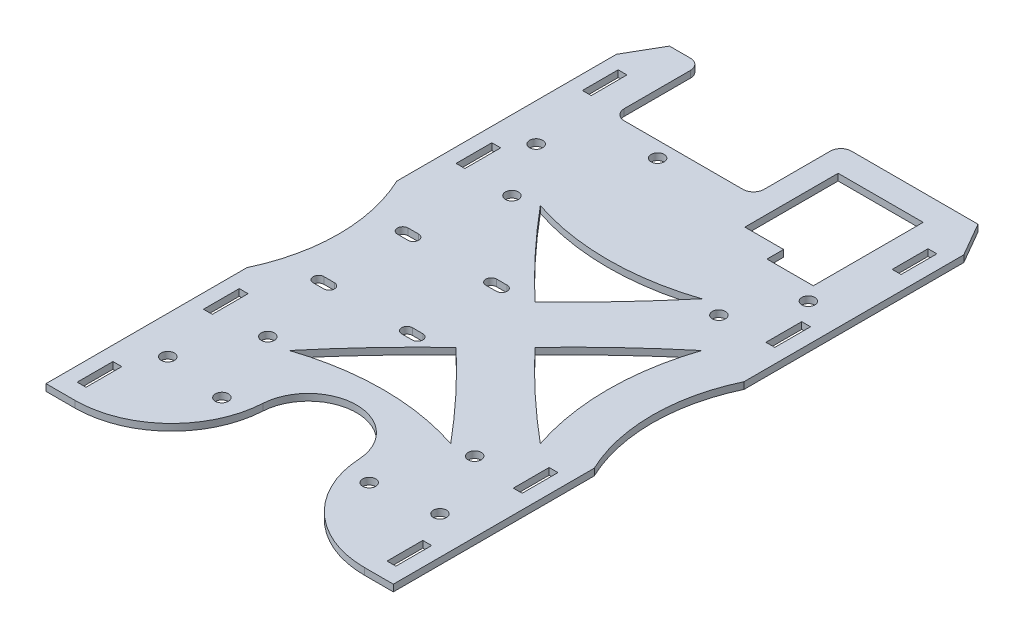
SolidWorks part; units mm, degrees
ref_plane "Front Plane" through (0, 0, 0) normal (0, 0, 1) x (1, 0, 0)
ref_plane "Top Plane" through (0, 0, 0) normal (0, 1, 0) x (1, 0, 0)
ref_plane "Right Plane" through (0, 0, 0) normal (1, 0, 0) x (0, 0, -1)
sketch "Sketch1" plane through (0, 0, 0) normal (0, 1, 0) x (1, 0, 0)
  line L0 (-1000, 0) -> (49000, 0) construction
  line L1 (0, 0) -> (0, 100.3728) construction
  line L5 (-41.25, -55) -> (-34.3696, -55)
  line L6 (41.25, -55) -> (34.3696, -55)
  line L7 (9.55, 82.35) -> (29.75, 82.35)
  line L8 (29.75, 82.35) -> (29.75, 56.25)
  line L10 (9.55, 60.2) -> (9.55, 82.35)
  line L11 (35.75, 77.5) -> (37.85, 77.5)
  line L12 (37.85, 77.5) -> (37.85, 69)
  line L13 (37.85, 69) -> (35.75, 69)
  line L14 (35.75, 69) -> (35.75, 77.5)
  line L15 (35.75, 39) -> (35.75, 47.5)
  line L16 (35.75, 47.5) -> (37.85, 47.5)
  line L17 (37.85, 47.5) -> (37.85, 39)
  line L18 (37.85, 39) -> (35.75, 39)
  line L19 (35.75, 9) -> (35.75, 17.5) construction
  line L20 (35.75, 17.5) -> (37.85, 17.5) construction
  line L21 (37.85, 17.5) -> (37.85, 9) construction
  line L22 (37.85, 9) -> (35.75, 9) construction
  line L35 (35.75, -51) -> (35.75, -42.5)
  line L36 (35.75, -42.5) -> (37.85, -42.5)
  line L37 (37.85, -42.5) -> (37.85, -51)
  line L38 (-41.25, -55) -> (-41.25, 0)
  line L39 (9.55, 60.2) -> (18.75, 60.2)
  line L40 (37.85, -51) -> (35.75, -51)
  line L42 (18.75, 56.25) -> (18.75, 60.2)
  line L43 (-37.85, -51) -> (-37.85, -42.5)
  line L44 (-37.85, -42.5) -> (-35.75, -42.5)
  line L45 (-41.25, 0) -> (-41.25, 80.5)
  line L46 (41.25, -55) -> (41.25, 0)
  line L47 (41.25, 0) -> (41.25, 80.5)
  line L48 (-41.25, 80.5) -> (-36.6408, 88.4834)
  line L49 (-36.6408, 88.4834) -> (36.6408, 88.4834)
  line L50 (41.25, 80.5) -> (36.6408, 88.4834)
  line L51 (35.75, -21) -> (35.75, -12.5)
  line L52 (35.75, -12.5) -> (37.85, -12.5)
  line L53 (37.85, -12.5) -> (37.85, -21)
  line L54 (37.85, -21) -> (35.75, -21)
  line L55 (35.75, 69) -> (35.75, 39) construction
  line L56 (-37.85, 69) -> (-37.85, 77.5)
  line L57 (-37.85, 77.5) -> (-35.75, 77.5)
  line L58 (-35.75, 77.5) -> (-35.75, 69)
  line L59 (-35.75, 69) -> (-37.85, 69)
  line L60 (-37.85, 39) -> (-37.85, 47.5)
  line L61 (-37.85, 47.5) -> (-35.75, 47.5)
  line L62 (-35.75, 47.5) -> (-35.75, 39)
  line L63 (-35.75, 39) -> (-37.85, 39)
  line L64 (-37.85, 9) -> (-37.85, 17.5) construction
  line L65 (-37.85, 17.5) -> (-35.75, 17.5) construction
  line L66 (-35.75, 17.5) -> (-35.75, 9) construction
  line L67 (-35.75, 9) -> (-37.85, 9) construction
  line L68 (-37.85, -21) -> (-37.85, -12.5)
  line L69 (-37.85, -12.5) -> (-35.75, -12.5)
  line L70 (-35.75, -12.5) -> (-35.75, -21)
  line L71 (-35.75, -21) -> (-37.85, -21)
  line L72 (18.75, 56.25) -> (29.75, 56.25)
  line L74 (-35.75, -42.5) -> (-35.75, -51)
  line L75 (-35.75, -51) -> (-37.85, -51)
  circle A2 centre (-15, 64.0223) radius 1.55
  circle A3 centre (-17.5, -36.9777) radius 1.55
  circle A6 centre (17.5, -36.9777) radius 1.55
  arc A7 (-11.4407, -33.3184) -> (-34.3696, -55) centre (-34.3696, -32.0353) cw
  arc A8 (-11.4407, -33.3184) -> (0, -22.5) centre (0, -33.9586) cw
  arc A9 (11.4407, -33.3184) -> (34.3696, -55) centre (34.3696, -32.0353) ccw
  arc A10 (11.4407, -33.3184) -> (0, -22.5) centre (0, -33.9586) ccw
  circle A11 centre (32.325, 52.5) radius 2.75 construction
  circle A12 centre (32.325, 52.5) radius 1.55
  circle A13 centre (32.325, -35) radius 1.55
  circle A14 centre (32.325, -35) radius 2.75 construction
  circle A15 centre (-32.325, 52.5) radius 1.55
  circle A16 centre (-32.325, -35) radius 1.55
  circle A17 centre (-32.325, 52.5) radius 2.75 construction
  circle A18 centre (-32.325, -35) radius 2.75 construction
  circle A19 centre (-24.575, 39) radius 1.55
  circle A20 centre (24.575, 39) radius 1.55
  circle A21 centre (24.575, -19) radius 1.55
  circle A22 centre (-24.575, -19) radius 1.55
  point P20 (-41.25, 0)
  point P23 (0, 55)
  point P26 (41.25, 0)
  point P63 (24.25, 56.25)
  point P83 (0, 88.4834)
  dimension "D20" = 5.5
  dimension "D21" = 3.1
  dimension "D22" = 64.65
  dimension "D4" = 101
  dimension "D5" = 17.5
  dimension "D6" = 15
  dimension "D7" = 64.0223
  dimension "D8" = 120
  dimension "D9" = 55
  dimension "D10" = 2
  dimension "D11" = 5
  dimension "D12" = 2.1
  dimension "D13" = 80.5
  dimension "D14" = 82.5
  dimension "D15" = 8.5
  dimension "D16" = 77.5
  dimension "D17" = 30
  dimension "D18" = 71.5
  dimension "D19" = 22.5
  dimension "D23" = 3.425
  dimension "D24" = 52.5
  dimension "D25" = 35
  dimension "D26" = 9.55
  dimension "D27" = 29.75
  dimension "D28" = 82.35
  dimension "D29" = 3.95
  dimension "D30" = 9.2
  dimension "D31" = 26.1
  dimension "D32" = 49.15
  dimension "D33" = 58
  dimension "D34" = 39
extrude "主结构和连接" add sketch "Sketch1" along normal blind 1.6 contours A10 A9 L6 L46 L47 L50 L49 L48 L45 L38 L5 A7 A8 L72 L42 L39 L10 L7 L8 L20 L21 L17 L12 L13 L14 L15 L19 region at (-0.9568, 0, -19.3532)
sketch "外部切除点示意-1" plane through (0, 0, 0) normal (0, 1, 0) x (1, 0, 0)
  line L0 (-36.6408, 88.4834) -> (36.6408, 88.4834) construction
  line L1 (0, 0) -> (-149.6598, 0) construction
  line L2 (0, -1000) -> (0, 49000) construction
  line L3 (-41.25, 28.3195) -> (-41.2859, -7.3505)
  line L4 (41.25, 28.3195) -> (41.2859, -7.3505)
  line L5 (4.0667, 88.4834) -> (4.0667, 67.7334)
  line L7 (4.0667, 67.7334) -> (-29.1468, 67.7334)
  line L8 (-29.1468, 67.7334) -> (-29.1468, 88.4834)
  line L10 (-29.1468, 88.4834) -> (4.0667, 88.4834)
  arc A0 (-41.25, 28.3195) -> (-41.2859, -7.3505) centre (-78.8424, 10.5223) cw
  arc A3 (41.25, 28.3195) -> (41.2859, -7.3505) centre (78.8424, 10.5223) ccw
  dimension "D1" = 20.75
extrude "底板让位" cut sketch "外部切除点示意-1" along normal through all
sketch "电源模块接口-草图" plane through (0, 0, 0) normal (0, 1, 0) x (1, 0, 0)
  line L0 (-32.25, 18.75) -> (-4.75, 18.75) construction
  line L1 (-4.75, 18.75) -> (-4.75, -1.25) construction
  line L2 (-4.75, -1.25) -> (-32.25, -1.25) construction
  line L3 (-32.25, -1.25) -> (-32.25, 18.75) construction
  line L4 (-30.25, 18.75) -> (-27.75, 18.75) construction
  line L5 (-30.25, 20.025) -> (-27.75, 20.025)
  line L6 (-30.25, 17.475) -> (-27.75, 17.475)
  line L7 (-18.5, 18.75) -> (-18.5, -1.25) construction
  line L8 (-32.25, 8.75) -> (-4.75, 8.75) construction
  line L9 (-6.75, 18.75) -> (-9.25, 18.75) construction
  line L10 (-6.75, 20.025) -> (-9.25, 20.025)
  line L11 (-6.75, 17.475) -> (-9.25, 17.475)
  line L12 (-30.25, -1.25) -> (-27.75, -1.25) construction
  line L13 (-30.25, -2.525) -> (-27.75, -2.525)
  line L14 (-30.25, 0.025) -> (-27.75, 0.025)
  line L15 (-6.75, -1.25) -> (-9.25, -1.25) construction
  line L16 (-6.75, -2.525) -> (-9.25, -2.525)
  line L17 (-6.75, 0.025) -> (-9.25, 0.025)
  arc A0 (-30.25, 20.025) -> (-30.25, 17.475) centre (-30.25, 18.75) ccw
  arc A1 (-27.75, 17.475) -> (-27.75, 20.025) centre (-27.75, 18.75) ccw
  arc A2 (-6.75, 20.025) -> (-6.75, 17.475) centre (-6.75, 18.75) cw
  arc A3 (-9.25, 17.475) -> (-9.25, 20.025) centre (-9.25, 18.75) cw
  arc A4 (-30.25, -2.525) -> (-30.25, 0.025) centre (-30.25, -1.25) cw
  arc A5 (-27.75, 0.025) -> (-27.75, -2.525) centre (-27.75, -1.25) cw
  arc A6 (-6.75, -2.525) -> (-6.75, 0.025) centre (-6.75, -1.25) ccw
  arc A7 (-9.25, 0.025) -> (-9.25, -2.525) centre (-9.25, -1.25) ccw
  point P6 (-29, 18.75)
  point P17 (-8, 18.75)
  point P24 (-29, -1.25)
  point P31 (-8, -1.25)
  dimension "D3" = 1.275
  dimension "D1" = 27.5
  dimension "D2" = 20
  dimension "D4" = 2.5
  dimension "D5" = 10.5
  dimension "D6" = 18.5
  dimension "D7" = 8.75
extrude "电源模块接口" cut sketch "电源模块接口-草图" along normal through all
sketch "草图2" plane through (0, 1.6, 0) normal (0, 1, 0) x (1, 0, 0)
  line L0 (0, 0) -> (0, 53.6886) construction
  line L1 (0, 0) -> (0, 100.3728) construction
  line L2 (0, 0) -> (139.6377, 0) construction
  line L3 (-201000, 0) -> (249000, 0) construction
  line L4 (0, 19.8942) -> (0, 10.5223) construction
  line L5 (0, 10.5223) -> (9.3719, 10.5223) construction
  arc A3 (9.3719, 10.5223) -> (29.8202, 29.7013) centre (187.9553, -159.3904) cw
  arc A4 (29.8202, 29.7013) -> (29.8202, -8.6566) centre (87.1283, 10.5223) ccw
  arc A5 (29.8202, -8.6566) -> (9.3719, 10.5223) centre (187.9553, 180.4351) cw
  circle A6 centre (0, 10.5223) radius 9.3719 construction
  arc A7 (0, 1.1505) -> (19.1789, -19.2978) centre (-169.9128, -177.433) cw
  arc A8 (19.1789, -19.2978) -> (-19.1789, -19.2978) centre (0, -76.6059) ccw
  arc A9 (-19.1789, -19.2978) -> (0, 1.1505) centre (169.9128, -177.433) cw
  arc A10 (-9.3719, 10.5223) -> (-29.8202, -8.6566) centre (-187.9553, 180.4351) cw construction
  arc A11 (-29.8202, -8.6566) -> (-29.8202, 29.7013) centre (-87.1283, 10.5223) ccw construction
  arc A12 (-29.8202, 29.7013) -> (-9.3719, 10.5223) centre (-187.9553, -159.3904) cw construction
  arc A13 (0, 19.8942) -> (-19.1789, 40.3425) centre (169.9128, 198.4777) cw
  arc A14 (-19.1789, 40.3425) -> (19.1789, 40.3425) centre (0, 97.6506) ccw
  arc A15 (19.1789, 40.3425) -> (0, 19.8942) centre (-169.9128, 198.4777) cw
  point P38 (0, 10.5223)
  dimension "D1" = 10.5223
  dimension "D2" = 4
extrude "飞控走线" cut sketch "草图2" against normal blind 10
fillet "圆角1" radius 2.5 4 edges at (-29.1468, 0.8, -67.7334) (4.0667, 0.8, -67.7334) (4.0667, 0.8, -88.4834) (-29.1468, 0.8, -88.4834)
